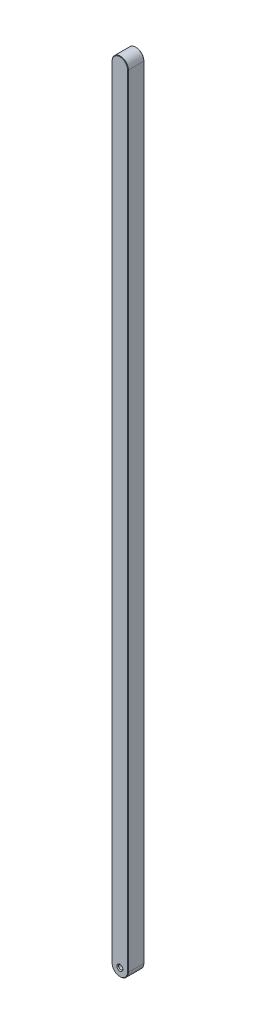
SolidWorks part; units mm, degrees
material "6061-T6 (SS)"
ref_plane "Front Plane" through (0, 0, 0) normal (0, 0, 1) x (1, 0, 0)
ref_plane "Top Plane" through (0, 0, 0) normal (0, 1, 0) x (1, 0, 0)
ref_plane "Right Plane" through (0, 0, 0) normal (1, 0, 0) x (0, 0, -1)
ref_axis "X Axis" through (88.99, 0, 0) along (-1, 0, 0)
ref_axis "Y Axis" through (0, 55, 0) along (0, -1, 0)
ref_axis "Z Axis" through (0, 0, -88.99) along (0, 0, 1)
sketch "Sketch1" plane through (0, 0, 0) normal (0, 0, 1) x (1, 0, 0)
  line L0 (0, 0) -> (0, 457.2) construction
  line L1 (-4.7625, 0) -> (-4.7625, 457.2)
  line L2 (4.7625, 0) -> (4.7625, 457.2)
  arc A0 (-4.7625, 0) -> (4.7625, 0) centre (0, 0) ccw
  arc A1 (4.7625, 457.2) -> (-4.7625, 457.2) centre (0, 457.2) ccw
  point P3 (0, 228.6)
  dimension "D1" = 9.525
  dimension "D2" = 457.2
extrude "Boss-Extrude1" add sketch "Sketch1" along normal mid plane 9.525
sketch "Sketch4" plane through (0, 0, 4.7625) normal (0, 0, 1) x (1, 0, 0)
  point P0 (0, 0)
hole_wizard "M3x0.5 Tapped Hole1" positions "Sketch4" profile "Sketch3" tap size "M3x0.5" standard "ANSI Metric" end condition through all
sketch "Sketch3" plane through (0, 0, 4.7625) normal (1, 0, 0) x (0, -1, 0)
  line L0 (0, 0) -> (0, 9.525)
  line L1 (0, 9.525) -> (1.75, 9.525)
  line L2 (1.25, 9.025) -> (1.25, 0.5)
  line L3 (1.25, 0.5) -> (1.75, 0)
  line L5 (1.75, 0) -> (0, 0)
  line L6 (-1.25, 0.5) -> (-1.75, 0) construction
  line L7 (1.75, 9.525) -> (1.25, 9.025)
  line L8 (-1.75, 9.525) -> (-1.25, 9.025) construction
  line L11 (0, -6.35) -> (0, 107.95) construction
  dimension "Thru Tap Drill Dia." = 2.5
  dimension "Thru Tap Drill Depth" = 9.525
  dimension "Near C'Sink Dia." = 3.5
  dimension "Near C'Sink Angle" = 90
  dimension "Far C'Sink Dia." = 3.5
  dimension "Far C'Sink Angle" = 90
cosmetic thread "Hole Thread1" parameters "D2"=3
chamfer "Chamfer1" distance 0.254 angle 45 8 edges at (4.7625, 228.6, -4.7625) (0, 461.9625, -4.7625) (-4.7625, 228.6, -4.7625) (0, -4.7625, -4.7625) (-4.7625, 228.6, 4.7625) (0, 461.9625, 4.7625) (4.7625, 228.6, 4.7625) (0, -4.7625, 4.7625)
